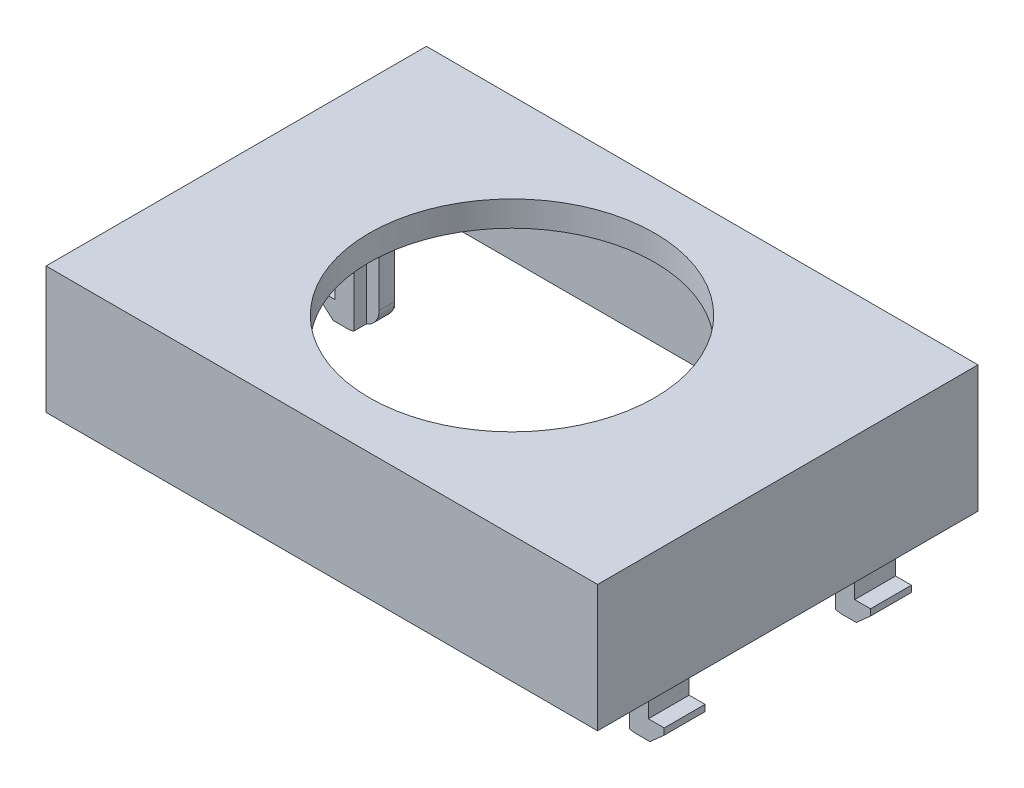
SolidWorks part; units mm, degrees
material "ABS PC"
ref_plane "Front Plane" through (0, 0, 0) normal (0, 0, 1) x (1, 0, 0)
ref_plane "Top Plane" through (0, 0, 0) normal (0, 1, 0) x (1, 0, 0)
ref_plane "Right Plane" through (0, 0, 0) normal (1, 0, 0) x (0, 0, -1)
sketch "Sketch1" plane through (0, 0, 0) normal (0, 1, 0) x (1, 0, 0)
  line L1 (-60.5581, 29.093) -> (26.4419, 29.093)
  line L2 (-60.5581, 29.093) -> (-60.5581, -30.907)
  line L3 (-60.5581, -30.907) -> (26.4419, -30.907)
  line L4 (26.4419, 29.093) -> (26.4419, -30.907)
  dimension "D1" = 60
  dimension "D2" = 87
extrude "Boss-Extrude1" add sketch "Sketch1" along normal blind 20
sketch "Sketch2" plane through (0, 20, 0) normal (0, 1, 0) x (1, 0, 0)
  line L0 (-60.5581, -30.907) -> (26.4419, -30.907) construction
  line L1 (-60.5581, 29.093) -> (-60.5581, -30.907) construction
  line L2 (26.4419, 29.093) -> (-60.5581, 29.093) construction
  line L3 (26.4419, -30.907) -> (26.4419, 29.093) construction
  circle A0 centre (-17.0581, -0.907) radius 22.5
  dimension "D2" = 45
  dimension "D1" = 30
  dimension "D3" = 43.5
  dimension "D4" = 30
  dimension "D5" = 43.5
extrude "Cut-Extrude1" cut sketch "Sketch2" against normal blind 20
sketch "Sketch3" plane through (0, 0, 0) normal (0, -1, 0) x (1, 0, 0)
  line L0 (-60.5581, -29.093) -> (-60.5581, 30.907) construction
  line L1 (-58.0581, 28.407) -> (23.9419, 28.407)
  line L2 (-58.0581, 28.407) -> (-58.0581, -26.593)
  line L3 (-58.0581, -26.593) -> (23.9419, -26.593)
  line L4 (23.9419, 28.407) -> (23.9419, -26.593)
  line L5 (26.4419, 30.907) -> (26.4419, -29.093) construction
  line L6 (26.4419, -29.093) -> (-60.5581, -29.093) construction
  line L7 (-60.5581, 30.907) -> (26.4419, 30.907) construction
  dimension "D1" = 82
  dimension "D2" = 55
  dimension "D3" = 2.5
  dimension "D4" = 2.5
  dimension "D5" = 2.5
  dimension "D6" = 2.5
extrude "Cut-Extrude2" cut sketch "Sketch3" against normal offset from surface (16 mm away) 16 up to face at (-17.0581, 0, 23.407)
sketch "Sketch4" plane through (23.9419, 0, 0) normal (-1, 0, 0) x (0, 0, 1)
  line L0 (-26.593, 16) -> (28.407, 16) construction
  line L1 (-18.593, 16) -> (-12.143, 16)
  line L2 (-18.593, 16) -> (-18.593, -7.85)
  line L3 (-18.593, -7.85) -> (-12.143, -7.85)
  line L4 (-12.143, 16) -> (-12.143, -7.85)
  line L5 (-26.593, 16) -> (-26.593, 0) construction
  line L6 (13.957, 16) -> (13.957, -7.85)
  line L7 (13.957, 16) -> (20.407, 16)
  line L8 (20.407, 16) -> (20.407, -7.85)
  line L9 (13.957, -7.85) -> (20.407, -7.85)
  line L10 (28.407, 16) -> (28.407, 0) construction
  dimension "D1" = 6.45
  dimension "D2" = 8
  dimension "D4" = 8
  dimension "D5" = 23.85
  dimension "D3" = 2
extrude "Boss-Extrude2" add sketch "Sketch4" along normal blind 3
sketch "Sketch5" plane through (20.9419, 0, 0) normal (-1, 0, 0) x (0, 0, 1)
  line L0 (-18.593, -7.85) -> (-12.143, -7.85) construction
  line L1 (-16.593, 11.15) -> (-14.143, 11.15)
  line L2 (-16.593, 11.15) -> (-16.593, -7.85)
  line L3 (-16.593, -7.85) -> (-14.143, -7.85)
  line L4 (-14.143, 11.15) -> (-14.143, -7.85)
  line L5 (-18.593, 16) -> (-18.593, -7.85) construction
  line L6 (-12.143, 16) -> (-18.593, 16) construction
  line L7 (-12.143, -7.85) -> (-12.143, 16) construction
  dimension "D1" = 2
  dimension "D2" = 2.45
  dimension "D3" = 19
  dimension "D4" = 4.85
  dimension "D5" = 2
extrude "Boss-Extrude3" add sketch "Sketch5" along normal blind 2
fillet "Fillet5" radius 3 5 edges at (20.9419, -7.85, -17.593) (20.9419, -7.85, -13.143) (19.9419, -7.85, -16.593) (19.9419, -7.85, -14.143) (18.9419, -7.85, -15.368)
fillet "Fillet7" radius 2 3 edges at (19.9419, 11.15, -16.593) (19.9419, 11.15, -14.143) (18.9419, 11.15, -15.368)
sketch "Sketch6" plane through (20.9419, 0, 0) normal (-1, 0, 0) x (0, 0, 1)
  line L0 (13.957, -7.85) -> (20.407, -7.85) construction
  line L1 (15.957, 11.15) -> (18.407, 11.15)
  line L2 (15.957, 11.15) -> (15.957, -7.85)
  line L3 (15.957, -7.85) -> (18.407, -7.85)
  line L4 (18.407, 11.15) -> (18.407, -7.85)
  line L5 (13.957, 16) -> (13.957, 0) construction
  dimension "D1" = 2
  dimension "D2" = 2.45
  dimension "D3" = 19
extrude "Boss-Extrude4" add sketch "Sketch6" along normal blind 2
fillet "Fillet8" radius 3 5 edges at (20.9419, -7.85, 19.407) (19.9419, -7.85, 15.957) (19.9419, -7.85, 18.407) (18.9419, -7.85, 17.182) (20.9419, -7.85, 14.957)
fillet "Fillet9" radius 2 3 edges at (19.9419, 11.15, 15.957) (19.9419, 11.15, 18.407) (18.9419, 11.15, 17.182)
sketch "Sketch7" plane through (23.9419, 0, 0) normal (1, 0, 0) x (0, 0, -1)
  line L0 (-20.407, -7.85) -> (-20.407, 0) construction
  line L1 (-20.407, -4.85) -> (-13.957, -4.85)
  line L2 (-20.407, -4.85) -> (-20.407, -7.85)
  line L3 (-20.407, -7.85) -> (-13.957, -7.85)
  line L4 (-13.957, -4.85) -> (-13.957, -7.85)
  line L5 (-13.957, 0) -> (-20.407, 0) construction
  dimension "D1" = 3
  dimension "D2" = 6.45
  dimension "D3" = 4.85
extrude "Boss-Extrude5" add sketch "Sketch7" along normal blind 2.5
sketch "Sketch8" plane through (0, 0, 20.407) normal (0, 0, 1) x (1, 0, 0)
  line L0 (26.4419, -5.85) -> (24.1919, -7.85)
  line L1 (26.4419, -4.85) -> (26.4419, -7.85) construction
  line L2 (21.9419, -7.85) -> (26.4419, -7.85) construction
  line L3 (24.1919, -7.85) -> (26.4419, -7.85)
  line L4 (26.4419, -7.85) -> (26.4419, -5.85)
  dimension "D1" = 2.25
  dimension "D2" = 2
sketch "Sketch9" plane through (23.9419, 0, 0) normal (1, 0, 0) x (0, 0, -1)
  line L0 (12.143, -7.85) -> (12.143, 0) construction
  line L1 (12.143, -4.85) -> (18.593, -4.85)
  line L2 (12.143, -4.85) -> (12.143, -7.85)
  line L3 (12.143, -7.85) -> (18.593, -7.85)
  line L4 (18.593, -4.85) -> (18.593, -7.85)
  dimension "D1" = 3
extrude "Boss-Extrude6" add sketch "Sketch9" along normal blind 2.5
extrude "Cut-Extrude3" cut sketch "Sketch8" against normal through all
sketch "Sketch46" plane through (-58.0581, 0, 0) normal (1, 0, 0) x (0, 0, -1)
  line L0 (-23.407, 16) -> (21.593, 16) construction
  line L1 (-20.407, 16) -> (-13.957, 16)
  line L2 (-20.407, 16) -> (-20.407, -7.85)
  line L3 (-20.407, -7.85) -> (-13.957, -7.85)
  line L4 (-13.957, 16) -> (-13.957, -7.85)
  line L5 (-28.407, 16) -> (-28.407, 0) construction
  line L6 (12.143, 16) -> (12.143, -7.85)
  line L7 (12.143, 16) -> (18.593, 16)
  line L8 (18.593, 16) -> (18.593, -7.85)
  line L9 (12.143, -7.85) -> (18.593, -7.85)
  line L10 (26.593, 16) -> (26.593, 0) construction
  dimension "D1" = 8
  dimension "D2" = 6.45
  dimension "D3" = 23.85
  dimension "D5" = 8
  dimension "D4" = 2
extrude "Boss-Extrude22" add sketch "Sketch46" along normal blind 3
sketch "Sketch47" plane through (-55.0581, 0, 0) normal (1, 0, 0) x (0, 0, -1)
  line L0 (-20.407, -7.85) -> (-13.957, -7.85) construction
  line L1 (-18.407, 11.15) -> (-15.957, 11.15)
  line L2 (-18.407, 11.15) -> (-18.407, -7.85)
  line L3 (-18.407, -7.85) -> (-15.957, -7.85)
  line L4 (-15.957, 11.15) -> (-15.957, -7.85)
  line L5 (-20.407, 16) -> (-20.407, -7.85) construction
  dimension "D1" = 2
  dimension "D2" = 2.45
  dimension "D3" = 19
extrude "Boss-Extrude23" add sketch "Sketch47" along normal blind 2
sketch "Sketch48" plane through (-55.0581, 0, 0) normal (1, 0, 0) x (0, 0, -1)
  line L0 (12.143, -7.85) -> (18.593, -7.85) construction
  line L1 (14.143, 11.15) -> (16.593, 11.15)
  line L2 (14.143, 11.15) -> (14.143, -7.85)
  line L3 (14.143, -7.85) -> (16.593, -7.85)
  line L4 (16.593, 11.15) -> (16.593, -7.85)
  line L5 (12.143, 16) -> (12.143, -7.85) construction
  dimension "D1" = 2
  dimension "D2" = 2.45
  dimension "D3" = 19
extrude "Boss-Extrude24" add sketch "Sketch48" along normal blind 2
fillet "Fillet11" radius 3 5 edges at (-55.0581, -7.85, 19.407) (-55.0581, -7.85, 14.957) (-54.0581, -7.85, 18.407) (-54.0581, -7.85, 15.957) (-53.0581, -7.85, 17.182)
fillet "Fillet12" radius 3 5 edges at (-55.0581, -7.85, -13.143) (-55.0581, -7.85, -17.593) (-54.0581, -7.85, -14.143) (-54.0581, -7.85, -16.593) (-53.0581, -7.85, -15.368)
fillet "Fillet13" radius 2 3 edges at (-54.0581, 11.15, -14.143) (-54.0581, 11.15, -16.593) (-53.0581, 11.15, -15.368)
fillet "Fillet14" radius 2 3 edges at (-54.0581, 11.15, 18.407) (-54.0581, 11.15, 15.957) (-53.0581, 11.15, 17.182)
sketch "Sketch49" plane through (-58.0581, 0, 0) normal (-1, 0, 0) x (0, 0, 1)
  line L0 (13.957, -7.85) -> (13.957, 0) construction
  line L1 (13.957, -4.85) -> (20.407, -4.85)
  line L2 (13.957, -4.85) -> (13.957, -7.85)
  line L3 (13.957, -7.85) -> (20.407, -7.85)
  line L4 (20.407, -4.85) -> (20.407, -7.85)
  dimension "D1" = 3
extrude "Boss-Extrude25" add sketch "Sketch49" along normal blind 2.5
sketch "Sketch50" plane through (-58.0581, 0, 0) normal (-1, 0, 0) x (0, 0, 1)
  line L0 (-18.593, -7.85) -> (-18.593, 0) construction
  line L1 (-18.593, -4.85) -> (-12.143, -4.85)
  line L2 (-18.593, -4.85) -> (-18.593, -7.85)
  line L3 (-18.593, -7.85) -> (-12.143, -7.85)
  line L4 (-12.143, -4.85) -> (-12.143, -7.85)
  dimension "D1" = 3
extrude "Boss-Extrude26" add sketch "Sketch50" along normal blind 2.5
sketch "Sketch52" plane through (0, 0, -18.593) normal (0, 0, -1) x (-1, 0, 0)
  line L0 (60.5581, -5.85) -> (58.3081, -7.85)
  line L1 (60.5581, -4.85) -> (60.5581, -7.85) construction
  line L2 (56.0581, -7.85) -> (60.5581, -7.85) construction
  line L3 (58.3081, -7.85) -> (60.5581, -7.85)
  line L4 (60.5581, -7.85) -> (60.5581, -5.85)
  dimension "D1" = 2.25
  dimension "D2" = 2
extrude "Cut-Extrude8" cut sketch "Sketch52" against normal through all
